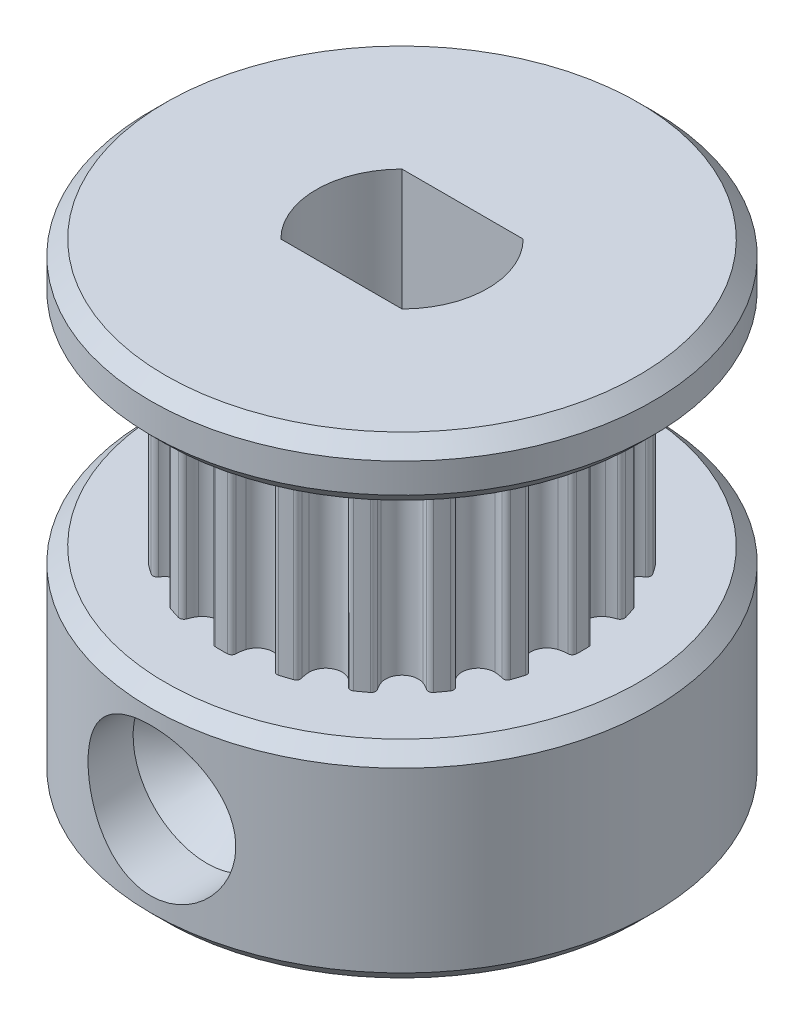
SolidWorks part; units mm, degrees
other "Markup1"
sketch "Sketch11" plane through (-10, 5.5, 10) normal (-0.2341, 0.0958, 0.9675) x (0.972, 0, 0.2351)
sketch "Sketch12" plane through (-9.5, 5.5, 9.5) normal (-0.2341, 0.0958, 0.9675) x (0.972, 0, 0.2351)
sketch "Sketch13" plane through (-9.5, 5.5, 9.5) normal (-0.2341, 0.0958, 0.9675) x (0.972, 0, 0.2351)
sketch "Sketch14" plane through (-8.5, 5.5, 8.5) normal (-0.2341, 0.0958, 0.9675) x (0.972, 0, 0.2351)
sketch "Sketch15" plane through (-8.5, 5.5, 8.5) normal (-0.2341, 0.0958, 0.9675) x (0.972, 0, 0.2351)
sketch "Sketch16" plane through (-8.5, 5.5, 8.5) normal (-0.2341, 0.0958, 0.9675) x (0.972, 0, 0.2351)
ref_plane "Front Plane" through (0, 0, 0) normal (0, 0, 1) x (1, 0, 0)
ref_plane "Top Plane" through (0, 0, 0) normal (0, 1, 0) x (1, 0, 0)
ref_plane "Right Plane" through (0, 0, 0) normal (1, 0, 0) x (0, 0, -1)
sketch "Sketch1" plane through (0, 0, 0) normal (0, 1, 0) x (1, 0, 0)
  line L0 (0, 0) -> (0, 6.3662) construction
  line L2 (0, 0) -> (0.9236, 5.8314) construction
  line L3 (0, 0) -> (1.4053, 6.2092) construction
  line L4 (1.3492, 5.9614) -> (1.2615, 5.4076) construction
  circle A0 centre (0, 0) radius 6.3662
  arc A1 (0.3928, 5.6692) -> (0.8368, 5.2832) centre (0.9236, 5.8314) ccw
  arc A2 (0.3492, 5.9592) -> (0.2042, 6.1088) centre (0.1992, 5.9589) ccw
  arc A3 (0.3492, 5.9592) -> (0.3928, 5.6692) centre (1.3492, 5.9614) ccw
  arc A4 (-0.3928, 5.6692) -> (-0.8368, 5.2832) centre (-0.9236, 5.8314) cw
  arc A5 (0.2042, 6.1088) -> (-0.2042, 6.1088) centre (0, 0) ccw
  arc A6 (-0.3492, 5.9592) -> (-0.3928, 5.6692) centre (-1.3492, 5.9614) cw
  arc A7 (-0.3492, 5.9592) -> (-0.2042, 6.1088) centre (-0.1992, 5.9589) cw
  arc A8 (1.3783, 5.5132) -> (0.8368, 5.2832) centre (0.9236, 5.8314) cw
  arc A9 (1.5094, 5.7754) -> (1.3783, 5.5132) centre (0.559, 6.0866) cw
  arc A10 (1.5094, 5.7754) -> (1.6935, 5.8729) centre (1.652, 5.7288) cw
  arc A11 (2.0819, 5.7467) -> (1.6935, 5.8729) centre (0, 0) ccw
  arc A12 (2.1736, 5.5596) -> (2.0819, 5.7467) centre (2.0308, 5.6057) ccw
  arc A13 (2.1736, 5.5596) -> (2.1255, 5.2704) centre (3.1253, 5.2527) ccw
  arc A14 (2.1255, 5.2704) -> (2.4284, 4.7661) centre (2.6804, 5.2606) ccw
  arc A15 (3.0145, 4.8174) -> (2.4284, 4.7661) centre (2.6804, 5.2606) cw
  arc A16 (3.2202, 5.0263) -> (3.0145, 4.8174) centre (2.4125, 5.6159) cw
  arc A17 (3.2202, 5.0263) -> (3.4255, 5.0621) centre (3.3414, 4.9379) cw
  arc A18 (3.7559, 4.8221) -> (3.4255, 5.0621) centre (0, 0) ccw
  arc A19 (3.7852, 4.6159) -> (3.7559, 4.8221) centre (3.6637, 4.7037) ccw
  arc A20 (3.7852, 4.6159) -> (3.6501, 4.3556) centre (4.5956, 4.0299) ccw
  arc A21 (3.6501, 4.3556) -> (3.7824, 3.7824) centre (4.1748, 4.1748) ccw
  arc A22 (4.3556, 3.6501) -> (3.7824, 3.7824) centre (4.1748, 4.1748) cw
  arc A23 (4.6159, 3.7852) -> (4.3556, 3.6501) centre (4.0299, 4.5956) cw
  arc A24 (4.6159, 3.7852) -> (4.8221, 3.7559) centre (4.7037, 3.6637) cw
  arc A25 (5.0621, 3.4255) -> (4.8221, 3.7559) centre (0, 0) ccw
  arc A26 (5.0263, 3.2202) -> (5.0621, 3.4255) centre (4.9379, 3.3414) ccw
  arc A27 (5.0263, 3.2202) -> (4.8174, 3.0145) centre (5.6159, 2.4125) ccw
  arc A28 (4.8174, 3.0145) -> (4.7661, 2.4284) centre (5.2606, 2.6804) ccw
  arc A29 (5.2704, 2.1255) -> (4.7661, 2.4284) centre (5.2606, 2.6804) cw
  arc A30 (5.5596, 2.1736) -> (5.2704, 2.1255) centre (5.2527, 3.1253) cw
  arc A31 (5.5596, 2.1736) -> (5.7467, 2.0819) centre (5.6057, 2.0308) cw
  arc A32 (5.8729, 1.6935) -> (5.7467, 2.0819) centre (0, 0) ccw
  arc A33 (5.7754, 1.5094) -> (5.8729, 1.6935) centre (5.7288, 1.652) ccw
  arc A34 (5.7754, 1.5094) -> (5.5132, 1.3783) centre (6.0866, 0.559) ccw
  arc A35 (5.5132, 1.3783) -> (5.2832, 0.8368) centre (5.8314, 0.9236) ccw
  arc A36 (5.6692, 0.3928) -> (5.2832, 0.8368) centre (5.8314, 0.9236) cw
  arc A37 (5.9592, 0.3492) -> (5.6692, 0.3928) centre (5.9614, 1.3492) cw
  arc A38 (5.9592, 0.3492) -> (6.1088, 0.2042) centre (5.9589, 0.1992) cw
  arc A39 (6.1088, -0.2042) -> (6.1088, 0.2042) centre (0, 0) ccw
  arc A40 (5.9592, -0.3492) -> (6.1088, -0.2042) centre (5.9589, -0.1992) ccw
  arc A41 (5.9592, -0.3492) -> (5.6692, -0.3928) centre (5.9614, -1.3492) ccw
  arc A42 (5.6692, -0.3928) -> (5.2832, -0.8368) centre (5.8314, -0.9236) ccw
  arc A43 (5.5132, -1.3783) -> (5.2832, -0.8368) centre (5.8314, -0.9236) cw
  arc A44 (5.7754, -1.5094) -> (5.5132, -1.3783) centre (6.0866, -0.559) cw
  arc A45 (5.7754, -1.5094) -> (5.8729, -1.6935) centre (5.7288, -1.652) cw
  arc A46 (5.7467, -2.0819) -> (5.8729, -1.6935) centre (0, 0) ccw
  arc A47 (5.5596, -2.1736) -> (5.7467, -2.0819) centre (5.6057, -2.0308) ccw
  arc A48 (5.5596, -2.1736) -> (5.2704, -2.1255) centre (5.2527, -3.1253) ccw
  arc A49 (5.2704, -2.1255) -> (4.7661, -2.4284) centre (5.2606, -2.6804) ccw
  arc A50 (4.8174, -3.0145) -> (4.7661, -2.4284) centre (5.2606, -2.6804) cw
  arc A51 (5.0263, -3.2202) -> (4.8174, -3.0145) centre (5.6159, -2.4125) cw
  arc A52 (5.0263, -3.2202) -> (5.0621, -3.4255) centre (4.9379, -3.3414) cw
  arc A53 (4.8221, -3.7559) -> (5.0621, -3.4255) centre (0, 0) ccw
  arc A54 (4.6159, -3.7852) -> (4.8221, -3.7559) centre (4.7037, -3.6637) ccw
  arc A55 (4.6159, -3.7852) -> (4.3556, -3.6501) centre (4.0299, -4.5956) ccw
  arc A56 (4.3556, -3.6501) -> (3.7824, -3.7824) centre (4.1748, -4.1748) ccw
  arc A57 (3.6501, -4.3556) -> (3.7824, -3.7824) centre (4.1748, -4.1748) cw
  arc A58 (3.7852, -4.6159) -> (3.6501, -4.3556) centre (4.5956, -4.0299) cw
  arc A59 (3.7852, -4.6159) -> (3.7559, -4.8221) centre (3.6637, -4.7037) cw
  arc A60 (3.4255, -5.0621) -> (3.7559, -4.8221) centre (0, 0) ccw
  arc A61 (3.2202, -5.0263) -> (3.4255, -5.0621) centre (3.3414, -4.9379) ccw
  arc A62 (3.2202, -5.0263) -> (3.0145, -4.8174) centre (2.4125, -5.6159) ccw
  arc A63 (3.0145, -4.8174) -> (2.4284, -4.7661) centre (2.6804, -5.2606) ccw
  arc A64 (2.1255, -5.2704) -> (2.4284, -4.7661) centre (2.6804, -5.2606) cw
  arc A65 (2.1736, -5.5596) -> (2.1255, -5.2704) centre (3.1253, -5.2527) cw
  arc A66 (2.1736, -5.5596) -> (2.0819, -5.7467) centre (2.0308, -5.6057) cw
  arc A67 (1.6935, -5.8729) -> (2.0819, -5.7467) centre (0, 0) ccw
  arc A68 (1.5094, -5.7754) -> (1.6935, -5.8729) centre (1.652, -5.7288) ccw
  arc A69 (1.5094, -5.7754) -> (1.3783, -5.5132) centre (0.559, -6.0866) ccw
  arc A70 (1.3783, -5.5132) -> (0.8368, -5.2832) centre (0.9236, -5.8314) ccw
  arc A71 (0.3928, -5.6692) -> (0.8368, -5.2832) centre (0.9236, -5.8314) cw
  arc A72 (0.3492, -5.9592) -> (0.3928, -5.6692) centre (1.3492, -5.9614) cw
  arc A73 (0.3492, -5.9592) -> (0.2042, -6.1088) centre (0.1992, -5.9589) cw
  arc A74 (-0.2042, -6.1088) -> (0.2042, -6.1088) centre (0, 0) ccw
  arc A75 (-0.3492, -5.9592) -> (-0.2042, -6.1088) centre (-0.1992, -5.9589) ccw
  arc A76 (-0.3492, -5.9592) -> (-0.3928, -5.6692) centre (-1.3492, -5.9614) ccw
  arc A77 (-0.3928, -5.6692) -> (-0.8368, -5.2832) centre (-0.9236, -5.8314) ccw
  arc A78 (-1.3783, -5.5132) -> (-0.8368, -5.2832) centre (-0.9236, -5.8314) cw
  arc A79 (-1.5094, -5.7754) -> (-1.3783, -5.5132) centre (-0.559, -6.0866) cw
  arc A80 (-1.5094, -5.7754) -> (-1.6935, -5.8729) centre (-1.652, -5.7288) cw
  arc A81 (-2.0819, -5.7467) -> (-1.6935, -5.8729) centre (0, 0) ccw
  arc A82 (-2.1736, -5.5596) -> (-2.0819, -5.7467) centre (-2.0308, -5.6057) ccw
  arc A83 (-2.1736, -5.5596) -> (-2.1255, -5.2704) centre (-3.1253, -5.2527) ccw
  arc A84 (-2.1255, -5.2704) -> (-2.4284, -4.7661) centre (-2.6804, -5.2606) ccw
  arc A85 (-3.0145, -4.8174) -> (-2.4284, -4.7661) centre (-2.6804, -5.2606) cw
  arc A86 (-3.2202, -5.0263) -> (-3.0145, -4.8174) centre (-2.4125, -5.6159) cw
  arc A87 (-3.2202, -5.0263) -> (-3.4255, -5.0621) centre (-3.3414, -4.9379) cw
  arc A88 (-3.7559, -4.8221) -> (-3.4255, -5.0621) centre (0, 0) ccw
  arc A89 (-3.7852, -4.6159) -> (-3.7559, -4.8221) centre (-3.6637, -4.7037) ccw
  arc A90 (-3.7852, -4.6159) -> (-3.6501, -4.3556) centre (-4.5956, -4.0299) ccw
  arc A91 (-3.6501, -4.3556) -> (-3.7824, -3.7824) centre (-4.1748, -4.1748) ccw
  arc A92 (-4.3556, -3.6501) -> (-3.7824, -3.7824) centre (-4.1748, -4.1748) cw
  arc A93 (-4.6159, -3.7852) -> (-4.3556, -3.6501) centre (-4.0299, -4.5956) cw
  arc A94 (-4.6159, -3.7852) -> (-4.8221, -3.7559) centre (-4.7037, -3.6637) cw
  arc A95 (-5.0621, -3.4255) -> (-4.8221, -3.7559) centre (0, 0) ccw
  arc A96 (-5.0263, -3.2202) -> (-5.0621, -3.4255) centre (-4.9379, -3.3414) ccw
  arc A97 (-5.0263, -3.2202) -> (-4.8174, -3.0145) centre (-5.6159, -2.4125) ccw
  arc A98 (-4.8174, -3.0145) -> (-4.7661, -2.4284) centre (-5.2606, -2.6804) ccw
  arc A99 (-5.2704, -2.1255) -> (-4.7661, -2.4284) centre (-5.2606, -2.6804) cw
  arc A100 (-5.5596, -2.1736) -> (-5.2704, -2.1255) centre (-5.2527, -3.1253) cw
  arc A101 (-5.5596, -2.1736) -> (-5.7467, -2.0819) centre (-5.6057, -2.0308) cw
  arc A102 (-5.8729, -1.6935) -> (-5.7467, -2.0819) centre (0, 0) ccw
  arc A103 (-5.7754, -1.5094) -> (-5.8729, -1.6935) centre (-5.7288, -1.652) ccw
  arc A104 (-5.7754, -1.5094) -> (-5.5132, -1.3783) centre (-6.0866, -0.559) ccw
  arc A105 (-5.5132, -1.3783) -> (-5.2832, -0.8368) centre (-5.8314, -0.9236) ccw
  arc A106 (-5.6692, -0.3928) -> (-5.2832, -0.8368) centre (-5.8314, -0.9236) cw
  arc A107 (-5.9592, -0.3492) -> (-5.6692, -0.3928) centre (-5.9614, -1.3492) cw
  arc A108 (-5.9592, -0.3492) -> (-6.1088, -0.2042) centre (-5.9589, -0.1992) cw
  arc A109 (-6.1088, 0.2042) -> (-6.1088, -0.2042) centre (0, 0) ccw
  arc A110 (-5.9592, 0.3492) -> (-6.1088, 0.2042) centre (-5.9589, 0.1992) ccw
  arc A111 (-5.9592, 0.3492) -> (-5.6692, 0.3928) centre (-5.9614, 1.3492) ccw
  arc A112 (-5.6692, 0.3928) -> (-5.2832, 0.8368) centre (-5.8314, 0.9236) ccw
  arc A113 (-5.5132, 1.3783) -> (-5.2832, 0.8368) centre (-5.8314, 0.9236) cw
  arc A114 (-5.7754, 1.5094) -> (-5.5132, 1.3783) centre (-6.0866, 0.559) cw
  arc A115 (-5.7754, 1.5094) -> (-5.8729, 1.6935) centre (-5.7288, 1.652) cw
  arc A116 (-5.7467, 2.0819) -> (-5.8729, 1.6935) centre (0, 0) ccw
  arc A117 (-5.5596, 2.1736) -> (-5.7467, 2.0819) centre (-5.6057, 2.0308) ccw
  arc A118 (-5.5596, 2.1736) -> (-5.2704, 2.1255) centre (-5.2527, 3.1253) ccw
  arc A119 (-5.2704, 2.1255) -> (-4.7661, 2.4284) centre (-5.2606, 2.6804) ccw
  arc A120 (-4.8174, 3.0145) -> (-4.7661, 2.4284) centre (-5.2606, 2.6804) cw
  arc A121 (-5.0263, 3.2202) -> (-4.8174, 3.0145) centre (-5.6159, 2.4125) cw
  arc A122 (-5.0263, 3.2202) -> (-5.0621, 3.4255) centre (-4.9379, 3.3414) cw
  arc A123 (-4.8221, 3.7559) -> (-5.0621, 3.4255) centre (0, 0) ccw
  arc A124 (-4.6159, 3.7852) -> (-4.8221, 3.7559) centre (-4.7037, 3.6637) ccw
  arc A125 (-4.6159, 3.7852) -> (-4.3556, 3.6501) centre (-4.0299, 4.5956) ccw
  arc A126 (-4.3556, 3.6501) -> (-3.7824, 3.7824) centre (-4.1748, 4.1748) ccw
  arc A127 (-3.6501, 4.3556) -> (-3.7824, 3.7824) centre (-4.1748, 4.1748) cw
  arc A128 (-3.7852, 4.6159) -> (-3.6501, 4.3556) centre (-4.5956, 4.0299) cw
  arc A129 (-3.7852, 4.6159) -> (-3.7559, 4.8221) centre (-3.6637, 4.7037) cw
  arc A130 (-3.4255, 5.0621) -> (-3.7559, 4.8221) centre (0, 0) ccw
  arc A131 (-3.2202, 5.0263) -> (-3.4255, 5.0621) centre (-3.3414, 4.9379) ccw
  arc A132 (-3.2202, 5.0263) -> (-3.0145, 4.8174) centre (-2.4125, 5.6159) ccw
  arc A133 (-3.0145, 4.8174) -> (-2.4284, 4.7661) centre (-2.6804, 5.2606) ccw
  arc A134 (-2.1255, 5.2704) -> (-2.4284, 4.7661) centre (-2.6804, 5.2606) cw
  arc A135 (-2.1736, 5.5596) -> (-2.1255, 5.2704) centre (-3.1253, 5.2527) cw
  arc A136 (-2.1736, 5.5596) -> (-2.0819, 5.7467) centre (-2.0308, 5.6057) cw
  arc A137 (-1.6935, 5.8729) -> (-2.0819, 5.7467) centre (0, 0) ccw
  arc A138 (-1.5094, 5.7754) -> (-1.6935, 5.8729) centre (-1.652, 5.7288) ccw
  arc A139 (-1.5094, 5.7754) -> (-1.3783, 5.5132) centre (-0.559, 6.0866) ccw
  arc A140 (-1.3783, 5.5132) -> (-0.8368, 5.2832) centre (-0.9236, 5.8314) ccw
  point P4 (0, 6.1122)
  point P11 (0, 6.3662)
  point P67 (0, 0)
  dimension "D1" = 12.7324
  dimension "D3" = 1
  dimension "D4" = 0.555
  dimension "D2" = 0.15
  dimension "D5" = 0.4
  dimension "D8" = 0.254
  dimension "D7" = 9
  dimension "D6" = 0.254
  dimension "D9" = 20
extrude "Gear" add sketch "Sketch1" along normal mid plane 7 contours A140 A139 A138 A137 A136 A135 A134 A133 A132 A131 A130 A129 A128 A127 A126 A125 A124 A123 A122 A121 A120 A119 A118 A117 A116 A115 A114 A113 A112 A111 A110 A109 A108 A107 A106 A105 A104 A103 A102 A101 A100 A99 A98 A97 A96 A95 A94 A93 A92 A91 A90 region at (0, 0, 0)
sketch "Sketch2" plane through (0, -3.5, 0) normal (0, -1, 0) x (1, 0, 0)
  line L0 (-11.7249, 0) -> (11.7249, 0) construction
  line L1 (-1.9666, 1.85) -> (1.9666, 1.85)
  line L2 (-1.9666, -1.85) -> (1.9666, -1.85)
  line L3 (-2.0512, -2.05) -> (2.0512, -2.05)
  line L4 (-2.0512, 2.05) -> (2.0512, 2.05)
  arc A0 (-1.9666, 1.85) -> (-1.9666, -1.85) centre (0, 0) ccw
  arc A1 (1.9666, -1.85) -> (1.9666, 1.85) centre (0, 0) ccw
  arc A2 (2.0512, -2.05) -> (2.0512, 2.05) centre (0, 0) ccw
  arc A3 (-2.0512, 2.05) -> (-2.0512, -2.05) centre (0, 0) ccw
  circle A4 centre (0, 0) radius 8.5
  point P4 (0, 0)
  dimension "D2" = 5.4
  dimension "D4" = 17
  dimension "D1" = 3.7
  dimension "D3" = 0.2
extrude "Base" add sketch "Sketch2" along normal blind 7 contours A4 L0 A3 L4 A2 | L0 A4 A2 L3 A3 region at (0, -3.5, 3.8849) region at (0, -3.5, -3.8849)
sketch "Sketch3" plane through (0, 0, 0) normal (0, 0, 1) x (1, 0, 0)
  line L0 (0, 0) -> (0, -7) construction
  line L1 (0, -10.06) -> (2.65, -8.53)
  line L2 (2.65, -8.53) -> (2.65, -5.47)
  line L3 (2.65, -5.47) -> (0, -3.94)
  line L4 (0, -3.94) -> (-2.65, -5.47)
  line L5 (-2.65, -5.47) -> (-2.65, -8.53)
  line L6 (-2.65, -8.53) -> (0, -10.06)
  line L7 (-2.65, -8.53) -> (-2.65, -10.5)
  line L8 (-8.5, -10.5) -> (8.5, -10.5) construction
  line L9 (-2.65, -10.5) -> (2.65, -10.5)
  line L10 (2.65, -10.5) -> (2.65, -8.53)
  circle A0 centre (0, -7) radius 2.65 construction
  dimension "D1" = 5.3
  dimension "D2" = 7
extrude "Nut Passthrough" cut sketch "Sketch3" along normal blind 4.2 contours L9 L10 L1 L6 L7 | L5 L6 L1 L2 L3 L4 region at (0, -7, 0) region at (1.3533, -9.3439, 0)
sketch "Sketch9" plane through (0, 3.5, 0) normal (0, 1, 0) x (1, 0, 0)
  circle A0 centre (0, 0) radius 8.5
  dimension "D1" = 17
extrude "Top" add sketch "Sketch9" along normal blind 2
extrude "Shaft Hole" cut sketch "Sketch2<4>" against normal through all contours A0 L0 A1 L1 | L0 A0 L2 A1 | L0 A3 L3 A2 A1 L2 A0 | A3 L0 A0 L1 A1 A2 L4 region at (-2.6226, -3.5, 1.0859) region at (-2.8, -3.5, -0.0615) region at (0, -3.5, 0.8808) region at (0, -3.5, -0.8808)
sketch "Sketch2<4>" plane through (0, -3.5, 0) normal (0, -1, 0) x (1, 0, 0) same geometry as "Sketch2"
extrude "Boss-Extrude4" add sketch "Sketch2<5>" along normal blind 7 separate body contours L0 A0 L2 A1 | A0 L0 A1 L1 region at (0, -3.5, 0.8808) region at (0, -3.5, -0.8808)
sketch "Sketch2<5>" plane through (0, -3.5, 0) normal (0, -1, 0) x (1, 0, 0) same geometry as "Sketch2"
sketch "Sketch10" plane through (0, 0, 0) normal (0, 0, 1) x (1, 0, 0)
  circle A0 centre (0, -7) radius 1.4
  circle A1 centre (0, -7) radius 2.5
  dimension "D1" = 2.8
  dimension "D2" = 5
extrude "Screw Hole" cut sketch "Sketch10" along normal through all contours A0 region at (0, -7, 0)
extrude "Screw Counterbore" cut sketch "Sketch10<3>" along normal through all from offset 5.5
sketch "Sketch10<3>" plane through (0, 0, 0) normal (0, 0, 1) x (1, 0, 0) same geometry as "Sketch10"
chamfer "Chamfer1" distance 0.5 angle 45 4 edges at (0, -3.5, -8.5) (0, -10.5, -8.5) (0, 3.5, 8.5) (0, 5.5, 8.5)
chamfer "Chamfer2" distance 1.1 angle 45 1 edges at (2.5, -7, 5.5)
equation "\"D1@Sketch1\"=\"pd\""
equation "\"teethNum\"= 20"
equation "\"pitch\"= 2mm"
equation "\"pd\"= \"teethNum\" * \"pitch\" / PI"
equation "\"D9@Sketch1\"=\"teethNum\""
equation "\"outerDia\"= 17"
equation "\"D4@Sketch2\"=\"outerDia\""
equation "\"D1@Sketch9\"=\"outerDia\""
equation "\"D7@Sketch1\"=180/ \"teethNum\""
